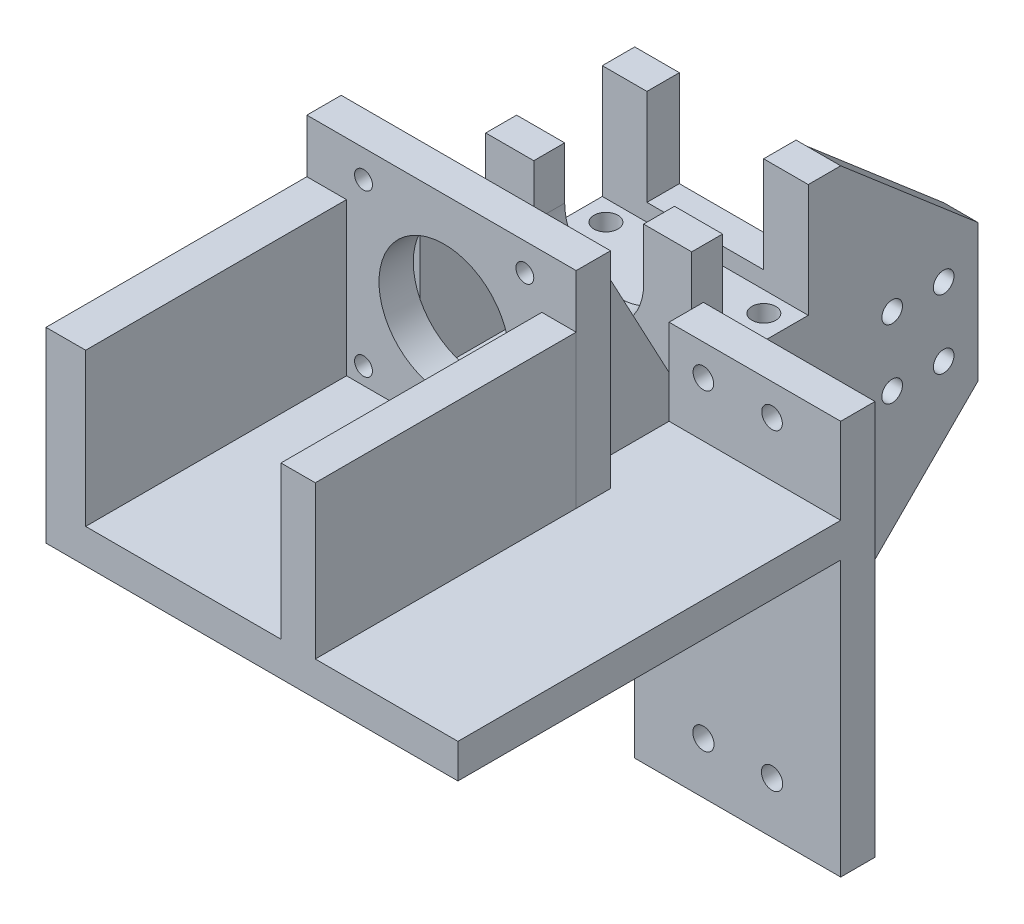
SolidWorks part; units mm, degrees
ref_plane "Front Plane" through (0, 0, 0) normal (0, 0, 1) x (1, 0, 0)
ref_plane "Top Plane" through (0, 0, 0) normal (0, 1, 0) x (1, 0, 0)
ref_plane "Right Plane" through (0, 0, 0) normal (1, 0, 0) x (0, 0, -1)
sketch "Sketch1" plane through (0, 0, 0) normal (0, 1, 0) x (1, 0, 0)
  line L0 (0, 0) -> (0, 161.51)
  line L1 (0, 161.51) -> (60, 161.51)
  line L2 (60, 161.51) -> (60, 121.51)
  line L3 (60, 121.51) -> (110, 121.51)
  line L4 (110, 121.51) -> (110, 0)
  line L5 (110, 0) -> (0, 0)
  dimension "D1" = 161.51
  dimension "D2" = 60
  dimension "D3" = 50
  dimension "D4" = 121.51
extrude "Boss-Extrude1" add sketch "Sketch1" along normal blind 10
sketch "Sketch2" plane through (0, 10, 0) normal (0, 1, 0) x (1, 0, 0)
  line L0 (0, 161.51) -> (0, 0) construction
  line L1 (0, 152.1) -> (60, 152.1)
  line L2 (0, 152.1) -> (0, 127.1)
  line L3 (0, 127.1) -> (60, 127.1)
  line L4 (60, 152.1) -> (60, 127.1)
  line L5 (60, 121.51) -> (60, 161.51) construction
  line L6 (60, 161.51) -> (0, 161.51) construction
  dimension "D1" = 9.41
  dimension "D2" = 25
extrude "Boss-Extrude2" add sketch "Sketch2" along normal blind 6.45
sketch "Sketch3" plane through (0, 10, 0) normal (0, 1, 0) x (1, 0, 0)
  line L0 (60, 152.1) -> (60, 161.51) construction
  line L1 (0, 161.51) -> (60, 161.51)
  line L2 (0, 161.51) -> (0, 152.06)
  line L3 (0, 152.06) -> (60, 152.06)
  line L4 (60, 161.51) -> (60, 152.06)
  dimension "D1" = 9.45
extrude "Boss-Extrude3" add sketch "Sketch3" along normal blind 39.45
sketch "Sketch4" plane through (0, 0, -161.51) normal (0, 0, -1) x (-1, 0, 0)
  line L0 (-60, 49.45) -> (0, 49.45) construction
  line L1 (-47, 49.45) -> (-13, 49.45)
  line L2 (-47, 49.45) -> (-47, 21.45)
  line L3 (-47, 21.45) -> (-13, 21.45)
  line L4 (-13, 49.45) -> (-13, 21.45)
  line L5 (-60, 49.45) -> (-60, 0) construction
  line L6 (0, 49.45) -> (0, 0) construction
  dimension "D1" = 13
  dimension "D2" = 13
  dimension "D3" = 28
extrude "Cut-Extrude1" cut sketch "Sketch4" against normal blind 9.45
sketch "Sketch5" plane through (0, 10, 0) normal (0, 1, 0) x (1, 0, 0)
  line L0 (60, 127.1) -> (60, 152.06) construction
  line L1 (0, 127.1) -> (60, 127.1)
  line L2 (0, 127.1) -> (0, 118.1)
  line L3 (0, 118.1) -> (60, 118.1)
  line L4 (60, 127.1) -> (60, 118.1)
  dimension "D1" = 9
extrude "Boss-Extrude4" add sketch "Sketch5" along normal blind 39.45
sketch "Sketch6" plane through (0, 0, -118.1) normal (0, 0, 1) x (1, 0, 0)
  line L0 (30, 49.45) -> (30, 10) construction
  line L1 (0, 49.45) -> (60, 49.45) construction
  line L2 (0, 10) -> (60, 10) construction
  line L3 (14, 34.24) -> (14, 49.45)
  line L4 (14, 49.45) -> (46, 49.45)
  line L5 (46, 49.45) -> (46, 34.24)
  arc A0 (14, 34.24) -> (46, 34.24) centre (30, 34.24) ccw
  point P9 (0, 0)
  dimension "D1" = 16
  dimension "D2" = 15.21
extrude "Cut-Extrude2" cut sketch "Sketch6" against normal up to next
sketch "Sketch7" plane through (0, 0, 0) normal (0, -1, 0) x (1, 0, 0)
  line L0 (110, -111.51) -> (50, -111.51)
  line L1 (110, 0) -> (110, -121.51) construction
  line L2 (50, -111.51) -> (50, -161.51)
  line L3 (60, -161.51) -> (0, -161.51) construction
  line L4 (50, -161.51) -> (60, -161.51)
  line L5 (60, -161.51) -> (60, -121.51)
  line L6 (60, -121.51) -> (110, -121.51)
  line L7 (110, -121.51) -> (110, -111.51)
  dimension "D1" = 10
  dimension "D2" = 10
extrude "Boss-Extrude5" add sketch "Sketch7" along normal blind 80
sketch "Sketch8" plane through (0, 0, 0) normal (-1, 0, 0) x (0, 0, 1)
  line L0 (-161.51, 0) -> (0, 0) construction
  line L1 (-75.9971, 0) -> (0, 0)
  line L2 (-75.9971, 0) -> (-75.9971, 54.4584)
  line L3 (-75.9971, 54.4584) -> (0, 54.4584)
  line L4 (0, 0) -> (0, 54.4584)
  line L5 (0, 10) -> (0, 0) construction
  dimension "D1" = 75.9971
extrude "Boss-Extrude6" add sketch "Sketch8" along normal blind 10
sketch "Sketch9" plane through (0, 10, 0) normal (0, 1, 0) x (1, 0, 0)
  line L0 (0, 0) -> (110, 0) construction
  line L1 (58.45, 75.9971) -> (68.45, 75.9971)
  line L2 (58.45, 75.9971) -> (58.45, 0)
  line L3 (58.45, 0) -> (68.45, 0)
  line L4 (68.45, 75.9971) -> (68.45, 0)
  line L5 (0, 0) -> (0, 75.9971) construction
  line L6 (-10, 75.9971) -> (0, 75.9971) construction
  dimension "D1" = 58.45
  dimension "D2" = 10
extrude "Boss-Extrude7" add sketch "Sketch9" along normal blind 44.46
sketch "Sketch17" plane through (0, 10, 0) normal (0, 1, 0) x (1, 0, 0)
  line L0 (0, 0) -> (58.45, 0) construction
  line L1 (68.45, 86) -> (-10, 86)
  line L2 (68.45, 86) -> (68.45, 76)
  line L3 (68.45, 76) -> (-10, 76)
  line L4 (-10, 86) -> (-10, 76)
  line L5 (-10, 0) -> (-10, 75.9971) construction
  dimension "D1" = 78.45
  dimension "D2" = 10
  dimension "D3" = 76
  dimension "D4" = 78.45
extrude "Boss-Extrude27" add sketch "Sketch17" along normal blind 60
sketch "Sketch19" plane through (0, 0, -86) normal (0, 0, -1) x (-1, 0, 0)
  line L0 (0, 10) -> (10, 10) construction
  line L1 (0, 70) -> (-2.5, 70)
  line L2 (0, 70) -> (0, 10)
  line L3 (0, 10) -> (-2.5, 10)
  line L4 (-2.5, 70) -> (-2.5, 10)
  line L5 (10, 70) -> (10, 10) construction
  line L6 (-68.45, 70) -> (10, 70) construction
  line L7 (-13, 70) -> (-10.5, 70)
  line L8 (-13, 70) -> (-13, 10)
  line L9 (-13, 10) -> (-10.5, 10)
  line L10 (-10.5, 70) -> (-10.5, 10)
  line L12 (-47, 70) -> (-49.5, 70)
  line L13 (-47, 70) -> (-47, 10)
  line L14 (-47, 10) -> (-49.5, 10)
  line L15 (-49.5, 70) -> (-49.5, 10)
  line L16 (-57.5, 70) -> (-60, 70)
  line L17 (-57.5, 70) -> (-57.5, 10)
  line L18 (-57.5, 10) -> (-60, 10)
  line L19 (-60, 70) -> (-60, 10)
  dimension "D1" = 10
  dimension "D2" = 2.5
  dimension "D3" = 60
  dimension "D4" = 8
  dimension "D5" = 2.5
  dimension "D6" = 60
  dimension "D7" = 2.5
  dimension "D8" = 8
  dimension "D9" = 2.5
  dimension "D10" = 60
  dimension "D11" = 60
  dimension "D12" = 34
extrude "Boss-Extrude31" add sketch "Sketch19" along normal blind 32
sketch "Sketch20" plane through (0, 0, 0) normal (1, 0, 0) x (0, 0, -1)
  line L1 (0, 54.4584) -> (75.9971, 54.4584)
  line L2 (0, 54.4584) -> (0, 10)
  line L3 (0, 10) -> (75.9971, 10)
  line L4 (75.9971, 54.4584) -> (75.9971, 10)
extrude "Boss-Extrude32" add sketch "Sketch20" along normal blind 1.55
sketch "Sketch21" plane through (0, 0, -76) normal (0, 0, 1) x (1, 0, 0)
  line L0 (-10, 70) -> (-10, 10) construction
  line L1 (-10, 70) -> (68.45, 70) construction
  line L2 (53.5, 61.95) -> (6.5, 14.95) construction
  line L3 (53.5, 14.95) -> (6.5, 61.95) construction
  circle A0 centre (6.5, 61.95) radius 2.6
  circle A1 centre (53.5, 61.95) radius 2.6
  circle A2 centre (53.5, 14.95) radius 2.6
  circle A3 centre (6.5, 14.95) radius 2.6
  circle A4 centre (30, 38.45) radius 19
  dimension "D5" = 5.2
  dimension "D6" = 38
  dimension "D1" = 16.5
  dimension "D2" = 8.05
  dimension "D3" = 47
  dimension "D4" = 47
extrude "Cut-Extrude3" cut sketch "Sketch21" against normal blind 10
sketch "Sketch22" plane through (0, 0, 0) normal (0, -1, 0) x (1, 0, 0)
  line L0 (50, -161.51) -> (0, -161.51) construction
  line L1 (0, -161.51) -> (0, -75.9971) construction
  circle A0 centre (7.02, -146.1) radius 3.5
  circle A1 centre (7.02, -133) radius 3.5
  circle A2 centre (53.02, -146.1) radius 3.5
  circle A3 centre (53.02, -133) radius 3.5
  point P8 (0, 0)
  point P9 (0, 0)
  point P10 (0, 0)
  point P11 (0, 0)
  point P12 (0, 0)
  point P13 (0, 0)
  dimension "D4" = 7
  dimension "D1" = 13.1
  dimension "D2" = 15.41
  dimension "D3" = 7.02
  dimension "D5" = 46
extrude "Cut-Extrude4" cut sketch "Sketch22" against normal up to next
sketch "Sketch23" plane through (50, 0, 0) normal (-1, 0, 0) x (0, 0, 1)
  line L0 (-147.8691, 0) -> (-161.51, 0) construction
  line L1 (-153.1, 0) -> (-126.1, 0)
  line L2 (-153.1, 0) -> (-153.1, -6)
  line L3 (-153.1, -6) -> (-126.1, -6)
  line L4 (-126.1, 0) -> (-126.1, -6)
  line L10 (-161.51, -80) -> (-161.51, 0) construction
  dimension "D1" = 27
  dimension "D2" = 8.41
  dimension "D3" = 6
extrude "Cut-Extrude5" cut sketch "Sketch23" against normal up to next
sketch "Sketch24" plane through (50, 0, 0) normal (-1, 0, 0) x (0, 0, 1)
  line L0 (-161.51, -80) -> (-161.51, 0) construction
  line L1 (-111.51, -80) -> (-111.51, 0) construction
  line L2 (-111.51, -80) -> (-161.51, -80) construction
  circle A0 centre (-151.51, -15) radius 3.1
  circle A1 centre (-151.51, -65) radius 3.1
  circle A2 centre (-131.51, -15) radius 3.1
  circle A3 centre (-131.51, -65) radius 3.1
  point P10 (0, 0)
  point P11 (0, 0)
  point P12 (0, 0)
  dimension "D5" = 6.2
  dimension "D1" = 10
  dimension "D2" = 20
  dimension "D3" = 15
  dimension "D4" = 50
extrude "Cut-Extrude6" cut sketch "Sketch24" against normal up to next
sketch "Sketch25" plane through (0, 0, -111.51) normal (0, 0, 1) x (1, 0, 0)
  line L0 (50, -80) -> (50, 0) construction
  line L1 (110, -80) -> (50, -80) construction
  circle A0 centre (70, -15) radius 3.1
  circle A1 centre (90, -15) radius 3.1
  circle A2 centre (70, -65) radius 3.1
  circle A3 centre (90, -65) radius 3.1
  point P8 (0, 0)
  point P9 (0, 0)
  point P10 (0, 0)
  point P11 (0, 0)
  dimension "D5" = 6.2
  dimension "D1" = 20
  dimension "D2" = 20
  dimension "D3" = 15
  dimension "D4" = 50
extrude "Cut-Extrude7" cut sketch "Sketch25" against normal up to next
sketch "Sketch26" plane through (0, 0, 0) normal (-1, 0, 0) x (0, 0, 1)
  line L2 (-118.1, 10) -> (-86, 70)
  line L3 (-86, 70) -> (-118, 70)
  line L4 (-118, 70) -> (-118.1, 10)
extrude "Cut-Extrude10" cut sketch "Sketch26" against normal blind 70
sketch "Sketch27" plane through (0, 10, 0) normal (0, 1, 0) x (1, 0, 0)
  line L0 (60, 118) -> (60, 86) construction
  line L1 (110, 121.51) -> (60, 121.51)
  line L2 (110, 121.51) -> (110, 111.51)
  line L3 (110, 111.51) -> (60, 111.51)
  line L4 (60, 121.51) -> (60, 111.51)
  dimension "D1" = 10
extrude "Boss-Extrude33" add sketch "Sketch27" along normal blind 25
sketch "Sketch28" plane through (0, 0, -111.51) normal (0, 0, 1) x (1, 0, 0)
  line L0 (110, 35) -> (110, 10) construction
  line L1 (60, 35) -> (110, 35) construction
  circle A0 centre (90, 25.935) radius 3
  circle A1 centre (70, 25.935) radius 3
  point P4 (0, 0)
  point P5 (0, 0)
  dimension "D1" = 6
  dimension "D2" = 20
  dimension "D3" = 20
  dimension "D4" = 9.065
extrude "Cut-Extrude11" cut sketch "Sketch28" against normal up to next
sketch "Sketch29" plane through (0, 0, -161.51) normal (0, 0, -1) x (-1, 0, 0)
  line L0 (-60, 49.45) -> (-60, -80) construction
  line L1 (-60, 15.15) -> (-50, 15.15)
  line L2 (-60, 15.15) -> (-60, -24.85)
  line L3 (-60, -24.85) -> (-50, -24.85)
  line L4 (-50, 15.15) -> (-50, -24.85)
  line L5 (-50, -80) -> (-50, 0) construction
  line L6 (-60, 49.45) -> (-47, 49.45) construction
  dimension "D1" = 40
  dimension "D2" = 34.3
extrude "Boss-Extrude34" add sketch "Sketch29" along normal blind 40
sketch "Sketch30" plane through (50, 0, 0) normal (-1, 0, 0) x (0, 0, 1)
  line L0 (-201.51, 15.15) -> (-161.51, 15.15) construction
  line L1 (-201.51, -24.85) -> (-161.51, -24.85) construction
  line L2 (-201.51, -24.85) -> (-201.51, 15.15) construction
  circle A0 centre (-191.51, 5.15) radius 3
  circle A1 centre (-176.51, 5.15) radius 3
  circle A2 centre (-191.51, -14.85) radius 3
  circle A3 centre (-176.51, -14.85) radius 3
  point P8 (0, 0)
  point P9 (0, 0)
  point P10 (0, 0)
  point P11 (0, 0)
  dimension "D1" = 6
  dimension "D2" = 10
  dimension "D3" = 10
  dimension "D4" = 10
  dimension "D5" = 15
extrude "Cut-Extrude12" cut sketch "Sketch30" against normal up to next
sketch "Sketch31" plane through (50, 0, 0) normal (-1, 0, 0) x (0, 0, 1)
  line L0 (-161.51, 15.15) -> (-161.51, 49.45)
  line L1 (-161.51, 49.45) -> (-201.51, 15.15)
  line L2 (-201.51, 15.15) -> (-161.51, 15.15)
  line L3 (-161.51, -24.85) -> (-201.51, -24.85)
  line L4 (-201.51, -24.85) -> (-161.51, -64.85)
  line L5 (-161.51, -80) -> (-161.51, -24.85) construction
  line L6 (-161.51, -64.85) -> (-161.51, -24.85)
  dimension "D1" = 45
extrude "Boss-Extrude35" add sketch "Sketch31" against normal blind 10
